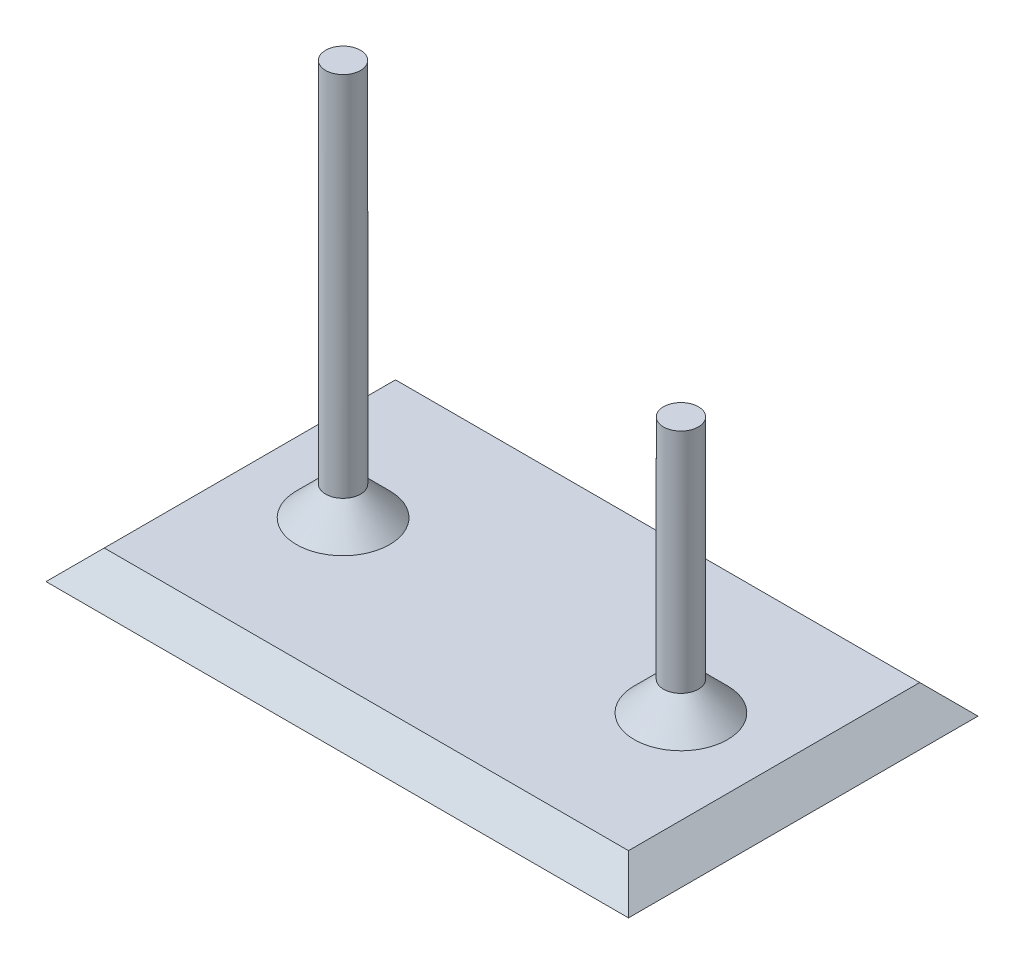
SolidWorks part; units mm, degrees
ref_plane "Front Plane" through (0, 0, 0) normal (0, 0, 1) x (1, 0, 0)
ref_plane "Top Plane" through (0, 0, 0) normal (0, 1, 0) x (1, 0, 0)
ref_plane "Right Plane" through (0, 0, 0) normal (1, 0, 0) x (0, 0, -1)
sketch "Sketch1" plane through (0, 0, 0) normal (0, 1, 0) x (1, 0, 0)
  line L1 (0, 38.1) -> (63.5, 38.1)
  line L2 (0, 38.1) -> (0, 0)
  line L3 (0, 0) -> (63.5, 0)
  line L4 (63.5, 38.1) -> (63.5, 0)
  dimension "D1" = 63.5
  dimension "D2" = 38.1
extrude "Boss-Extrude1" add sketch "Sketch1" along normal blind 3.175
sketch "Sketch2" plane through (0, 3.175, 0) normal (0, 1, 0) x (1, 0, 0)
  line L0 (13.335, 19.05) -> (50.165, 19.05) construction
  line L1 (63.5, 38.1) -> (0, 38.1) construction
  line L2 (63.5, 0) -> (63.5, 38.1) construction
  circle A0 centre (13.335, 19.05) radius 1.905
  circle A1 centre (50.165, 19.05) radius 1.905
  point P2 (31.75, 19.05)
  point P5 (31.75, 38.1)
  point P6 (63.5, 19.05)
  dimension "D1" = 3.81
  dimension "D2" = 36.83
extrude "Boss-Extrude2" add sketch "Sketch2" along normal blind 27.94
sketch "Sketch3" plane through (0, 31.115, 0) normal (0, 1, 0) x (1, 0, 0)
  circle A0 centre (13.335, 19.05) radius 1.905
extrude "Boss-Extrude3" add sketch "Sketch3" along normal blind 15.24
chamfer "Chamfer1" distance 3.175 angle 45 6 edges at (31.75, 3.175, -38.1) (63.5, 3.175, -19.05) (31.75, 3.175, 0) (0, 3.175, -19.05) (13.335, 3.175, -17.145) (50.165, 3.175, -17.145)
